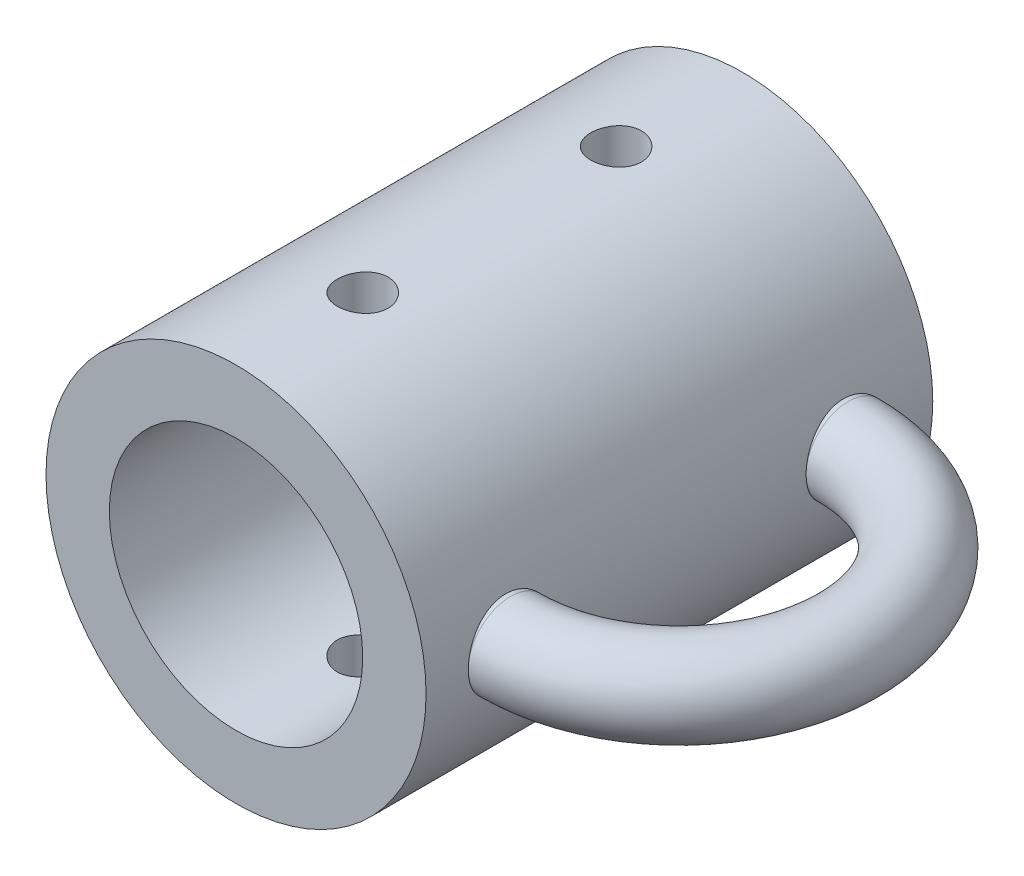
SolidWorks part; units mm, degrees
ref_plane "Front Plane" through (0, 0, 0) normal (0, 0, 1) x (1, 0, 0)
ref_plane "Top Plane" through (0, 0, 0) normal (0, 1, 0) x (1, 0, 0)
ref_plane "Right Plane" through (0, 0, 0) normal (1, 0, 0) x (0, 0, -1)
sketch "Sketch1" plane through (0, 0, 0) normal (0, 0, 1) x (1, 0, 0)
  circle A0 centre (0, 0) radius 15
  circle A1 centre (0, 0) radius 22.5
  dimension "D1" = 30
  dimension "D2" = 7.5
extrude "Boss-Extrude1" add sketch "Sketch1" along normal blind 30 and the other way blind 30
sketch "Sketch2" plane through (0, 0, 0) normal (0, 1, 0) x (1, 0, 0)
  circle A0 centre (0, -15) radius 3
  point P2 (0, 0)
  dimension "D1" = 6
  dimension "D2" = 15
extrude "Cut-Extrude1" cut sketch "Sketch2" along normal blind 30 and the other way blind 50
mirror "Mirror1" about plane through (0, 0, 0) normal (0, 0, 1) of "Cut-Extrude1"
sketch "Sketch3" plane through (0, 0, 0) normal (0, 1, 0) x (1, 0, 0)
  line L0 (22.5, -30) -> (22.5, 30) construction
  line L1 (22.5, -20) -> (20, -20)
  line L2 (22.5, 20) -> (20, 20)
  arc A0 (22.5, -20) -> (22.5, 20) centre (22.5, 0) ccw
  dimension "D1" = 20
  dimension "D2" = 20
  dimension "D3" = 22.5
  dimension "D4" = 2.5
ref_plane "Plane1" through (20, 0, 0) normal (1, 0, 0) x (0, 0, -1)
sketch "Sketch4" plane through (20, 0, 0) normal (1, 0, 0) x (0, 0, -1)
  line L0 (20, 0) -> (-20, 0) construction
  circle A0 centre (-20, 0) radius 5
  dimension "D2" = 10
  dimension "D1" = 20
sweep "Sweep2" add profiles "Sketch4" path "Sketch3"
